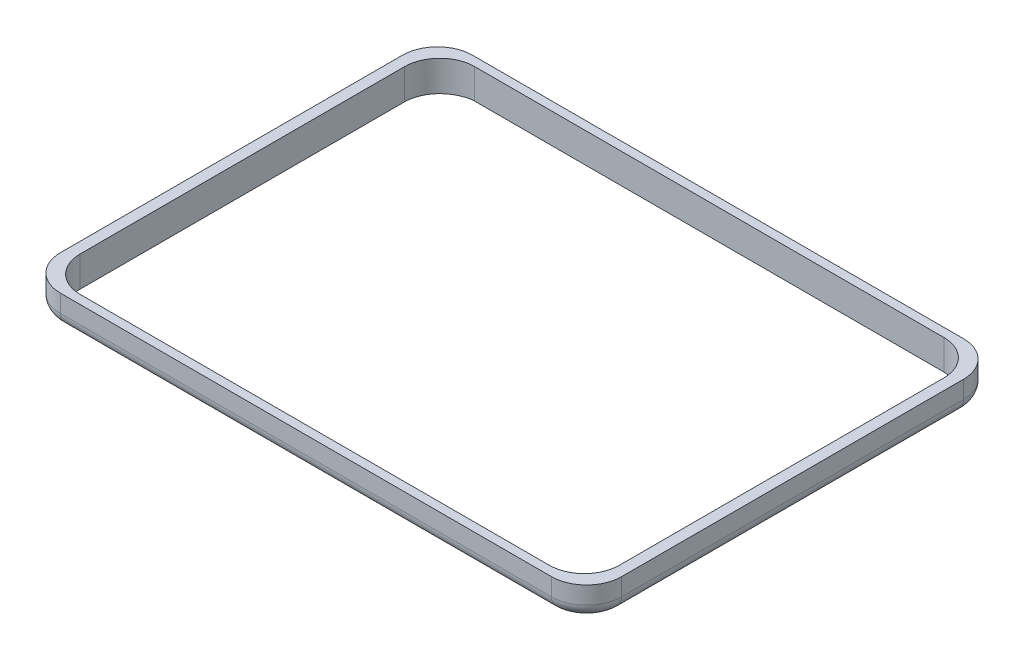
SolidWorks part; units mm, degrees
ref_plane "Front Plane" through (0, 0, 0) normal (0, 0, 1) x (1, 0, 0)
ref_plane "Top Plane" through (0, 0, 0) normal (0, 1, 0) x (1, 0, 0)
ref_plane "Right Plane" through (0, 0, 0) normal (1, 0, 0) x (0, 0, -1)
sketch "Sketch1" plane through (0, 0, 0) normal (0, 1, 0) x (1, 0, 0)
  line L0 (0, 0) -> (22.2675, 0) construction
  line L1 (-26.75, -22.5) -> (26.75, -22.5)
  line L2 (-30.75, -18.5) -> (-30.75, 18.5)
  line L3 (-26.75, 22.5) -> (26.75, 22.5)
  line L4 (30.75, -18.5) -> (30.75, 18.5)
  line L5 (0, 0) -> (0, 17.9267) construction
  line L7 (-28, 23.5) -> (28, 23.5)
  line L8 (-32, 19.5) -> (-32, -19.5)
  line L9 (-28, -23.5) -> (28, -23.5)
  line L10 (32, 19.5) -> (32, -19.5)
  arc A0 (26.75, 22.5) -> (30.75, 18.5) centre (26.75, 18.5) cw
  arc A1 (26.75, -22.5) -> (30.75, -18.5) centre (26.75, -18.5) ccw
  arc A2 (-26.75, -22.5) -> (-30.75, -18.5) centre (-26.75, -18.5) cw
  arc A3 (-30.75, 18.5) -> (-26.75, 22.5) centre (-26.75, 18.5) cw
  arc A4 (28, 23.5) -> (32, 19.5) centre (28, 19.5) cw
  arc A5 (28, -23.5) -> (32, -19.5) centre (28, -19.5) ccw
  arc A6 (-32, -19.5) -> (-28, -23.5) centre (-28, -19.5) ccw
  arc A7 (-28, 23.5) -> (-32, 19.5) centre (-28, 19.5) ccw
  point P24 (32, -23.5)
  point P27 (-32, -23.5)
  dimension "D3" = 4
  dimension "D6" = 4
  dimension "D1" = 45
  dimension "D2" = 61.5
  dimension "D4" = 47
  dimension "D5" = 64
extrude "Boss-Extrude1" add sketch "Sketch1" along normal blind 3.5
fillet "Fillet2" radius 1.5 4 edges at (-30.8284, 0, -22.3284) (30.8284, 0, -22.3284) (30.8284, 0, 22.3284) (-30.8284, 0, 22.3284)
